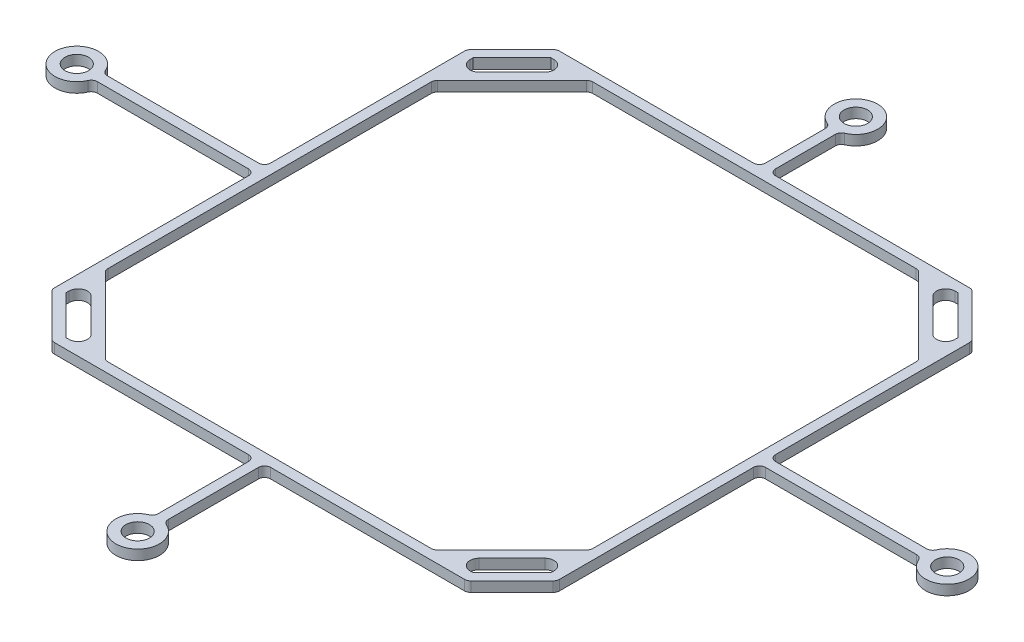
SolidWorks part; units mm, degrees
ref_plane "Front Plane" through (0, 0, 0) normal (0, 0, 1) x (1, 0, 0)
ref_plane "Top Plane" through (0, 0, 0) normal (0, 1, 0) x (1, 0, 0)
ref_plane "Right Plane" through (0, 0, 0) normal (1, 0, 0) x (0, 0, -1)
sketch "Sketch1" plane through (0, 0, 0) normal (0, 1, 0) x (1, 0, 0)
  line L0 (0, 0) -> (0, 56.4488) construction
  line L1 (0, 0) -> (-71.4488, 0) construction
  line L2 (-39.7988, 33.4083) -> (-33.4083, 39.7988)
  line L3 (-33.4083, -39.7988) -> (-29.2929, -39.7988)
  line L4 (-39.7988, -33.4083) -> (-39.7988, -29.2929)
  line L5 (-33.4083, 39.7988) -> (-29.2929, 39.7988)
  line L6 (39.7988, -33.4083) -> (39.7988, -29.2929)
  line L7 (-39.7988, -39.7988) -> (36.6035, 36.6035) construction
  line L8 (-36.6035, 36.6035) -> (39.7988, -39.7988) construction
  line L9 (33.4083, 39.7988) -> (39.7988, 33.4083)
  line L10 (39.7988, -33.4083) -> (33.4083, -39.7988)
  line L11 (-33.4083, -39.7988) -> (-39.7988, -33.4083)
  line L12 (-41.4488, 34.0917) -> (-34.0917, 41.4488)
  line L13 (34.0917, 41.4488) -> (0.825, 41.4488)
  line L14 (34.0917, 41.4488) -> (41.4488, 34.0917)
  line L15 (41.4488, -34.0917) -> (41.4488, -0.825)
  line L16 (41.4488, -34.0917) -> (34.0917, -41.4488)
  line L17 (-34.0917, -41.4488) -> (-0.825, -41.4488)
  line L18 (-34.0917, -41.4488) -> (-41.4488, -34.0917)
  line L19 (-41.4488, 34.0917) -> (-41.4488, 0.825)
  line L20 (-39.7988, 29.2929) -> (-29.2929, 39.7988)
  line L21 (-39.7988, 26.9594) -> (-26.9594, 39.7988)
  line L22 (29.2929, 39.7988) -> (39.7988, 29.2929)
  line L23 (26.9594, 39.7988) -> (39.7988, 26.9594)
  line L24 (39.7988, -29.2929) -> (29.2929, -39.7988)
  line L25 (39.7988, -26.9594) -> (26.9594, -39.7988)
  line L26 (-29.2929, -39.7988) -> (-39.7988, -29.2929)
  line L27 (-26.9594, -39.7988) -> (-39.7988, -26.9594)
  line L28 (-39.7988, 29.2929) -> (-39.7988, 33.4083)
  line L29 (-26.9594, 39.7988) -> (26.9594, 39.7988)
  line L30 (29.2929, 39.7988) -> (33.4083, 39.7988)
  line L31 (39.7988, 29.2929) -> (39.7988, 33.4083)
  line L32 (39.7988, -26.9594) -> (39.7988, 26.9594)
  line L33 (-39.7988, -26.9594) -> (-39.7988, 26.9594)
  line L34 (-26.9594, -39.7988) -> (26.9594, -39.7988)
  line L35 (29.2929, -39.7988) -> (33.4083, -39.7988)
  line L36 (67.9703, -0.825) -> (41.4488, -0.825)
  line L37 (0.825, 52.9703) -> (0.825, 41.4488)
  line L38 (-0.825, 52.9703) -> (-0.825, 41.4488)
  line L39 (67.9703, 0.825) -> (41.4488, 0.825)
  line L40 (-0.825, -57.9703) -> (-0.825, -41.4488)
  line L41 (0.825, -57.9703) -> (0.825, -41.4488)
  line L42 (-67.9703, 0.825) -> (-41.4488, 0.825)
  line L43 (-67.9703, -0.825) -> (-41.4488, -0.825)
  line L44 (0, 0) -> (0, -61.4488) construction
  line L45 (41.4488, 0.825) -> (41.4488, 34.0917)
  line L46 (-0.825, 41.4488) -> (-34.0917, 41.4488)
  line L47 (-41.4488, -0.825) -> (-41.4488, -34.0917)
  line L48 (0.825, -41.4488) -> (34.0917, -41.4488)
  arc A0 (0.825, 52.9703) -> (-0.825, 52.9703) centre (0, 56.4488) ccw
  circle A1 centre (0, 56.4488) radius 1.925
  circle A2 centre (71.4488, 0) radius 1.925
  arc A3 (67.9703, 0.825) -> (67.9703, -0.825) centre (71.4488, 0) cw
  arc A4 (-0.825, -57.9703) -> (0.825, -57.9703) centre (0, -61.4488) ccw
  circle A5 centre (0, -61.4488) radius 1.925
  arc A6 (-67.9703, 0.825) -> (-67.9703, -0.825) centre (-71.4488, 0) ccw
  circle A7 centre (-71.4488, 0) radius 1.925
  point P19 (0, 0)
  point P20 (0, 0)
  point P28 (0, 0)
  point P33 (0, 0)
  point P46 (0, 0)
  point P74 (0, 0)
  dimension "D10" = 3.85
  dimension "D11" = 1.65
  dimension "D15" = 1.65
  dimension "D16" = 3.85
  dimension "D20" = 3.85
  dimension "D21" = 1.65
  dimension "D1" = 1.65
  dimension "D2" = 79.5976
  dimension "D3" = 9.0376
  dimension "D5" = 1.65
  dimension "D6" = 4
  dimension "D7" = 2.91
  dimension "D8" = 1.65
  dimension "D12" = 0.825
  dimension "D13" = 0.825
  dimension "D14" = 15
  dimension "D17" = 30
  dimension "D18" = 0.825
  dimension "D19" = 0.825
  dimension "D22" = 0.825
  dimension "D23" = 0.825
  dimension "D24" = 20
  dimension "D25" = 12.8394
  dimension "D4" = 4
  dimension "D9" = 4
extrude "Boss-Extrude1" add sketch "Sketch1" along normal blind 1.65
fillet "Fillet4" radius 1 16 edges at (0.825, 0.825, -41.4488) (0.825, 0.825, -52.9703) (-0.825, 0.825, -52.9703) (-0.825, 0.825, -41.4488) (67.9703, 0.825, -0.825) (67.9703, 0.825, 0.825) (41.4488, 0.825, -0.825) (41.4488, 0.825, 0.825) (0.825, 0.825, 57.9703) (-0.825, 0.825, 57.9703) (-0.825, 0.825, 41.4488) (0.825, 0.825, 41.4488) (-41.4488, 0.825, 0.825) (-41.4488, 0.825, -0.825) (-67.9703, 0.825, 0.825) (-67.9703, 0.825, -0.825)
fillet "Fillet3" radius 1.5 8 edges at (29.2929, 0.825, 39.7988) (39.7988, 0.825, 29.2929) (-29.2929, 0.825, 39.7988) (-39.7988, 0.825, 29.2929) (-39.7988, 0.825, -29.2929) (-29.2929, 0.825, -39.7988) (39.7988, 0.825, -29.2929) (29.2929, 0.825, -39.7988)
fillet "Fillet5" radius 1 16 edges at (-26.9594, 0.825, 39.7988) (-39.7988, 0.825, 26.9594) (-41.4488, 0.825, 34.0917) (-34.0917, 0.825, 41.4488) (-39.7988, 0.825, -26.9594) (-26.9594, 0.825, -39.7988) (-41.4488, 0.825, -34.0917) (-34.0917, 0.825, -41.4488) (41.4488, 0.825, -34.0917) (34.0917, 0.825, -41.4488) (26.9594, 0.825, -39.7988) (39.7988, 0.825, -26.9594) (34.0917, 0.825, 41.4488) (41.4488, 0.825, 34.0917) (39.7988, 0.825, 26.9594) (26.9594, 0.825, 39.7988)
